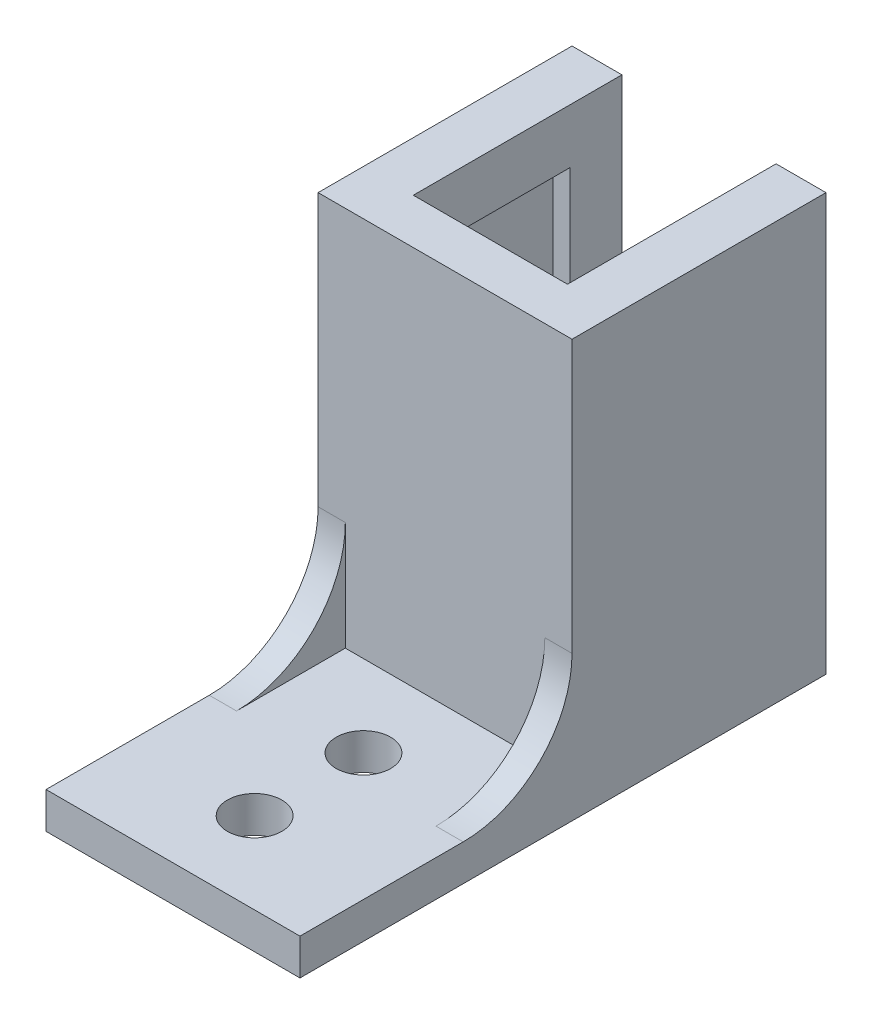
SolidWorks part; units mm, degrees
ref_plane "Front Plane" through (0, 0, 0) normal (0, 0, 1) x (1, 0, 0)
ref_plane "Top Plane" through (0, 0, 0) normal (0, 1, 0) x (1, 0, 0)
ref_plane "Right Plane" through (0, 0, 0) normal (1, 0, 0) x (0, 0, -1)
sketch "Sketch1" plane through (0, 0, 0) normal (0, 0, 1) x (1, 0, 0)
  line L1 (7, 11.5) -> (-7, 11.5)
  line L2 (7, 11.5) -> (7, -11.5)
  line L3 (7, -11.5) -> (-7, -11.5)
  line L4 (-7, 11.5) -> (-7, -11.5)
  line L5 (7, 11.5) -> (-7, -11.5) construction
  line L6 (7, -11.5) -> (-7, 11.5) construction
  point P0 (0, 0)
  dimension "D1" = 14
  dimension "D2" = 23
extrude "Boss-Extrude1" add sketch "Sketch1" along normal blind 14 contours L4 | L1 L4 L3 L2 | L2 region at (0, 0, 0)
sketch "Sketch2" plane through (0, -11.5, 0) normal (0, -1, 0) x (1, 0, 0)
  line L1 (5.2, 2.85) -> (-5.2, 2.85)
  line L2 (5.2, 2.85) -> (5.2, 11.5)
  line L3 (5.2, 11.5) -> (-5.2, 11.5)
  line L4 (-5.2, 2.85) -> (-5.2, 11.5)
  line L8 (4.25, 2.85) -> (-4.25, 2.85)
  line L9 (4.25, 2.85) -> (4.25, 0)
  line L10 (4.25, 0) -> (-4.25, 0)
  line L11 (-4.25, 2.85) -> (-4.25, 0)
  point P4 (0, 2.85)
  point P16 (0, 0)
  line M10 (7, 0) -> (7, 14)
  line M12 (-7, 14) -> (-7, 0)
  dimension "D1" = 11.5
  dimension "D2" = 8.65
  dimension "D3" = 10.4
  dimension "D4" = 8.5
extrude "Cut-Extrude1" cut sketch "Sketch2" against normal blind 20 contours L4 L1 L2 L3 | L1 L11 L9 | M10 | M12 region at (0, -11.5, 7.175) region at (0, -11.5, 1.425)
sketch "Sketch3" plane through (0, -11.5, 0) normal (0, -1, 0) x (1, 0, 0)
  line L0 (0, 18.5) -> (0, 24.5) construction
  line L1 (7, 14) -> (-7, 14)
  line L2 (7, 14) -> (7, 29)
  line L3 (7, 29) -> (-7, 29)
  line L4 (-7, 14) -> (-7, 29)
  circle A0 centre (0, 18.5) radius 1.5
  circle A1 centre (0, 24.5) radius 1.5
  point P10 (0, 21.5)
  point P11 (-7, 21.5)
  point P15 (0, 14)
  dimension "D1" = 3
  dimension "D2" = 6
  dimension "D3" = 4.5
extrude "Boss-Extrude2" add sketch "Sketch3" against normal blind 2
sketch "Sketch4" plane through (-7, 0, 0) normal (-1, 0, 0) x (0, 0, 1)
  line L1 (29, -9.5) -> (14, -9.5) construction
  line L2 (14, 11.5) -> (14, -9.5) construction
  line L3 (14, -3.5) -> (14, -9.5)
  line L4 (14, -9.5) -> (20, -9.5)
  arc A0 (20, -9.5) -> (14, -3.5) centre (20, -3.5) cw
  dimension "D1" = 6
extrude "Boss-Extrude3" add sketch "Sketch4" against normal blind 1.5
mirror "Mirror1" about plane through (0, 0, 0) normal (1, 0, 0) of "Boss-Extrude3"
sketch "Sketch5" plane through (0, 8.5, 0) normal (0, -1, 0) x (1, 0, 0)
  line L0 (5.2, 11.5) -> (-5.2, 11.5) construction
  line L1 (4.25, 0) -> (-4.25, 0)
  line L2 (4.25, 0) -> (4.25, 11.5)
  line L3 (4.25, 11.5) -> (-4.25, 11.5)
  line L4 (-4.25, 0) -> (-4.25, 11.5)
  line L5 (7, 0) -> (4.25, 0) construction
  line L6 (-4.25, 0) -> (4.25, 0) construction
extrude "Cut-Extrude2" cut sketch "Sketch5" against normal through all
sketch "Sketch6" plane through (0, 0, 0) normal (0, 0, -1) x (-1, 0, 0)
  line L0 (-7, 11.5) -> (-7, -11.5) construction
  line L1 (-7, 0) -> (7, 0)
  line L2 (-7, 0) -> (-7, -11.5)
  line L3 (-7, -11.5) -> (7, -11.5)
  line L4 (7, 0) -> (7, -11.5)
extrude "Cut-Extrude3" [suppressed] cut sketch "Sketch6" against normal through all
